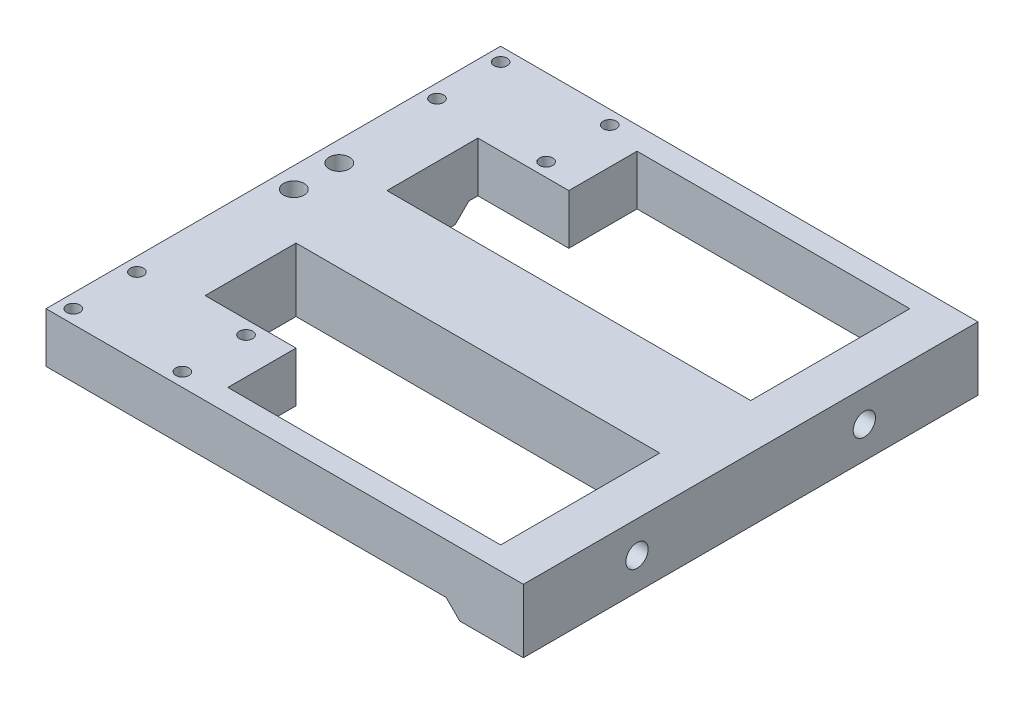
SolidWorks part; units mm, degrees
ref_plane "前视基准面" through (0, 0, 0) normal (0, 0, 1) x (1, 0, 0)
ref_plane "上视基准面" through (0, 0, 0) normal (0, 1, 0) x (1, 0, 0)
ref_plane "右视基准面" through (0, 0, 0) normal (1, 0, 0) x (0, 0, -1)
other "Configuration Table"
sketch "草图1" plane through (0, 0, 0) normal (0, 1, 0) x (1, 0, 0)
  line L1 (0, 0) -> (-105, 0)
  line L2 (0, 0) -> (0, 100)
  line L3 (0, 100) -> (-105, 100)
  line L4 (-105, 0) -> (-105, 100)
  dimension "D1" = 100
  dimension "D2" = 105
extrude "凸台-拉伸1" add sketch "草图1" along normal blind 16
sketch "草图6" plane through (0, 16, 0) normal (0, 1, 0) x (1, 0, 0)
  line L0 (-105, 100) -> (-105, 0) construction
  line L1 (-45.2241, 40) -> (-5, 40)
  line L2 (-70, 20) -> (-70, 5)
  line L3 (-70, 5) -> (-5, 5)
  line L4 (-5, 40) -> (-5, 5)
  line L5 (0, 0) -> (0, 100) construction
  line L6 (-105, 0) -> (0, 0) construction
  line L7 (-105, 50) -> (-60.5255, 50) construction
  line L8 (-70, 95) -> (-5, 95)
  line L9 (-5, 60) -> (-5, 95)
  line L10 (-45.2241, 60) -> (-5, 60)
  line L11 (-70, 80) -> (-70, 95)
  line L12 (-70, 80) -> (-100, 80)
  line L13 (-45.2241, 40) -> (-100, 40)
  line L15 (-70, 20) -> (-100, 20)
  line L16 (-100, 40) -> (-100, 20)
  line L17 (-45.2241, 60) -> (-100, 60)
  line L18 (-100, 60) -> (-100, 80)
  dimension "D1" = 35
  dimension "D2" = 5
  dimension "D3" = 5
  dimension "D4" = 20
  dimension "D5" = 30
  dimension "D6" = 20
extrude "切除-拉伸5" cut sketch "草图6" against normal up to next
sketch "草图8" plane through (0, 16, 0) normal (0, 1, 0) x (1, 0, 0)
  line L0 (-105, 100) -> (-102, 100) construction
  line L1 (0, 100) -> (-105, 100) construction
  line L2 (-102, 100) -> (-102, 97) construction
  line L3 (-102, 97) -> (-78, 97) construction
  line L4 (-78, 97) -> (-78, 83) construction
  line L5 (-78, 83) -> (-102, 83) construction
  line L6 (-105, 50) -> (-51.1245, 50) construction
  line L7 (-105, 100) -> (-105, 0) construction
  line L8 (-78, 17) -> (-102, 17) construction
  line L9 (-78, 3) -> (-78, 17) construction
  line L10 (-102, 3) -> (-78, 3) construction
  line L11 (-102, 0) -> (-102, 3) construction
  line L12 (-105, 0) -> (-102, 0) construction
  circle A0 centre (-102, 97) radius 1.45
  circle A1 centre (-102, 83) radius 1.45
  circle A2 centre (-78, 97) radius 1.45
  circle A3 centre (-78, 83) radius 1.45
  circle A4 centre (-78, 17) radius 1.45
  circle A5 centre (-78, 3) radius 1.45
  circle A6 centre (-102, 17) radius 1.45
  circle A7 centre (-102, 3) radius 1.45
  dimension "D6" = 2.9
  dimension "D7" = 2.9
  dimension "D8" = 2.9
  dimension "D9" = 2.9
  dimension "D1" = 3
  dimension "D2" = 3
  dimension "D3" = 24
  dimension "D4" = 14
  dimension "D5" = 24
extrude "切除-拉伸7" cut sketch "草图8" against normal through all
sketch "草图9" plane through (-5, 0, 0) normal (-1, 0, 0) x (0, 0, 1)
  line L0 (-40, 0) -> (-5, 0) construction
  line L1 (-5, 0) -> (-5, 16) construction
  line L2 (-5, 16) -> (-40, 16) construction
  line L3 (-40, 16) -> (-40, 0) construction
  line L4 (-95, 0) -> (-60, 0) construction
  line L5 (-60, 0) -> (-60, 16) construction
  line L6 (-60, 16) -> (-95, 16) construction
  line L7 (-95, 16) -> (-95, 0) construction
  line L8 (-40, 0) -> (-5, 0)
  line L9 (-5, 0) -> (-5, 16)
  line L10 (-5, 16) -> (-40, 16)
  line L11 (-40, 16) -> (-40, 0)
  line L12 (-95, 0) -> (-60, 0)
  line L13 (-60, 0) -> (-60, 16)
  line L14 (-60, 16) -> (-95, 16)
  line L15 (-95, 16) -> (-95, 0)
extrude "凸台-拉伸2" add sketch "草图9" along normal blind 5
sketch "草图12" plane through (-100, 0, 0) normal (1, 0, 0) x (0, 0, -1)
  line L0 (20, 0) -> (40, 0) construction
  line L1 (40, 0) -> (40, 16) construction
  line L2 (40, 16) -> (20, 16) construction
  line L3 (20, 16) -> (20, 0) construction
  line L4 (60, 0) -> (80, 0) construction
  line L5 (80, 0) -> (80, 16) construction
  line L6 (80, 16) -> (60, 16) construction
  line L7 (60, 16) -> (60, 0) construction
  line L8 (20, 0) -> (40, 0)
  line L9 (40, 0) -> (40, 16)
  line L10 (40, 16) -> (20, 16)
  line L11 (20, 16) -> (20, 0)
  line L12 (60, 0) -> (80, 0)
  line L13 (80, 0) -> (80, 16)
  line L14 (80, 16) -> (60, 16)
  line L15 (60, 16) -> (60, 0)
extrude "凸台-拉伸3" add sketch "草图12" along normal blind 10
sketch "草图13" plane through (0, 16, 0) normal (0, 1, 0) x (1, 0, 0)
  line L0 (-105, 50) -> (-100.5, 50) construction
  line L1 (-105, 100) -> (-105, 0) construction
  line L3 (-100.5, 50) -> (-100.5, 60) construction
  circle A0 centre (-100.5, 50) radius 2.25
  circle A1 centre (-100.5, 60) radius 2.25
  dimension "D4" = 4.5
  dimension "D5" = 4.5
  dimension "D3" = 10
  dimension "D6" = 4.5
  dimension "D1" = 4.5
  dimension "D2" = 10
extrude "切除-拉伸10" cut sketch "草图13" against normal blind 5
sketch "草图14" plane through (0, 0, 0) normal (0, -1, 0) x (1, 0, 0)
  line L4 (0, -100) -> (0, 0)
  line L5 (0, 0) -> (-105, 0)
  line L6 (-105, 0) -> (-105, -100)
  line L7 (-105, -100) -> (0, -100)
  line L9 (0, 0) -> (-105, 0)
  line L10 (-105, 0) -> (-105, -100)
  line L11 (-105, -100) -> (0, -100)
  line L13 (0, -100) -> (0, 0)
  dimension "D1" = 0
extrude "切除-拉伸11" cut sketch "草图14" against normal blind 2
sketch "草图16" plane through (0, 2, 0) normal (0, -1, 0) x (1, 0, 0)
  line L0 (-10, -40) -> (-10, -5) construction
  line L1 (-105, 0) -> (-14, 0)
  line L2 (-105, 0) -> (-105, -25)
  line L3 (-105, -25) -> (-14, -25)
  line L4 (-14, 0) -> (-14, -25)
  line L5 (-14, -75) -> (-105, -75)
  line L6 (-14, -75) -> (-14, -100)
  line L7 (-14, -100) -> (-105, -100)
  line L8 (-105, -75) -> (-105, -100)
  line L9 (-10, -95) -> (-10, -60) construction
  dimension "D1" = 4
  dimension "D2" = 4
extrude "切除-拉伸13" cut sketch "草图16" against normal blind 3
chamfer "倒角1" distance 3 angle 45 4 edges at (-14, 5, -2.5) (-97.5, 5, -25) (-97.5, 5, -75) (-14, 5, -97.5)
sketch "草图17" plane through (-105, 0, 0) normal (-1, 0, 0) x (0, 0, 1)
  line L0 (0, 9) -> (-55.4, 9) construction
  line L1 (0, 16) -> (0, 5) construction
  line L2 (-100, 16) -> (0, 16) construction
  circle A0 centre (-55.4, 9) radius 2.25
  dimension "D2" = 4.5
  dimension "D1" = 55.4
  dimension "D3" = 7
extrude "切除-拉伸14" cut sketch "草图17" against normal blind 5
sketch "草图18" plane through (-100, 0, 0) normal (-1, 0, 0) x (0, 0, 1)
  circle A0 centre (-55.4, 9) radius 1.5
  dimension "D1" = 3
extrude "切除-拉伸15" cut sketch "草图18" against normal blind 4
sketch "草图21" plane through (0, 0, 0) normal (1, 0, 0) x (0, 0, -1)
  line L0 (100, 16) -> (100, 2) construction
  line L1 (0, 16) -> (100, 16) construction
  line L2 (0, 16) -> (0, 2) construction
  circle A0 centre (25, 9) radius 2.45
  circle A1 centre (75, 9) radius 2.45
  dimension "D1" = 25
  dimension "D2" = 7
  dimension "D3" = 4.9
  dimension "D4" = 4.9
  dimension "D5" = 7
  dimension "D6" = 25
extrude "切除-拉伸17" cut sketch "草图21" against normal blind 13.2
